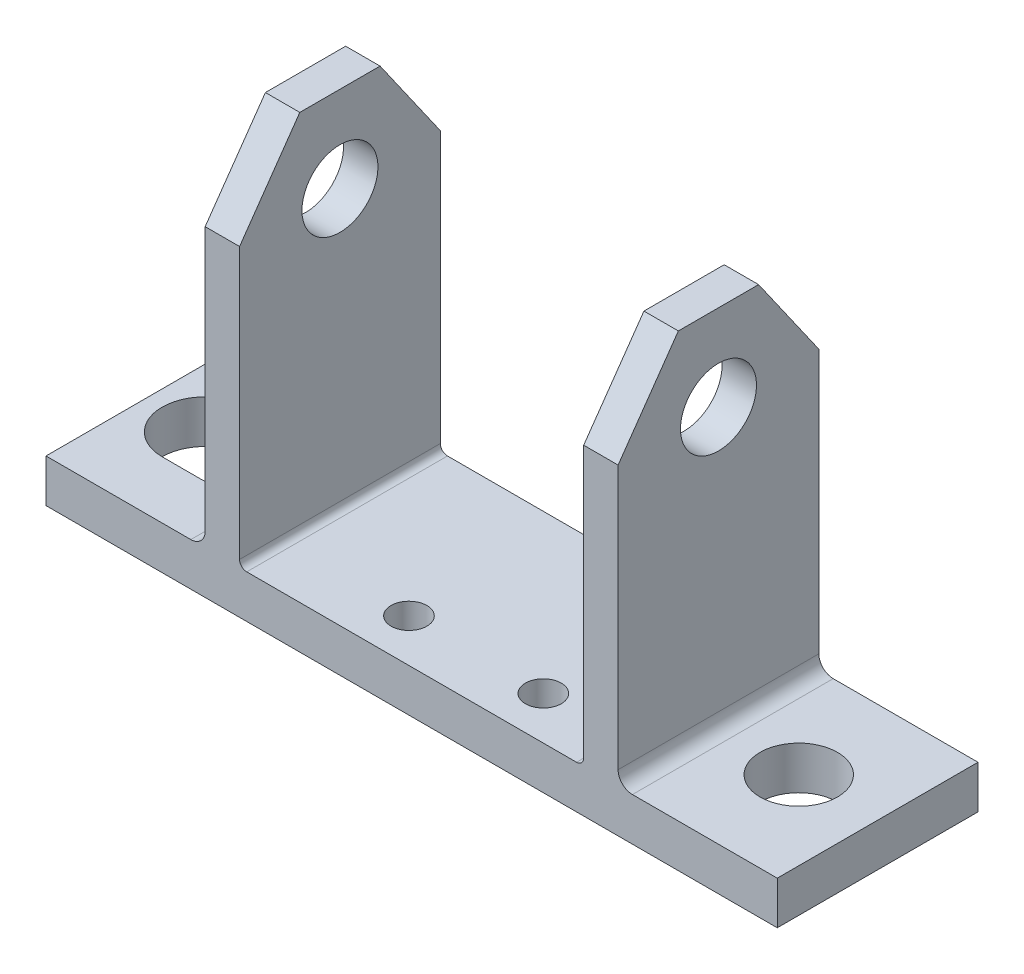
SolidWorks part; units mm, degrees
ref_plane "Front Plane" through (0, 0, 0) normal (0, 0, 1) x (1, 0, 0)
ref_plane "Top Plane" through (0, 0, 0) normal (0, 1, 0) x (1, 0, 0)
ref_plane "Right Plane" through (0, 0, 0) normal (1, 0, 0) x (0, 0, -1)
sketch "Sketch1" plane through (0, 0, 0) normal (0, 1, 0) x (1, 0, 0)
  line L0 (4.1, 7) -> (6.9, 7) construction
  line L1 (0, 0) -> (51, 0)
  line L2 (0, 0) -> (0, 14)
  line L3 (0, 14) -> (51, 14)
  line L4 (51, 0) -> (51, 14)
  line L5 (0, 0) -> (51, 14) construction
  line L6 (0, 14) -> (51, 0) construction
  line L7 (4.1, 10) -> (6.9, 10)
  line L8 (4.1, 4) -> (6.9, 4)
  line L12 (25.5, 14) -> (25.5, 0) construction
  arc A0 (4.1, 10) -> (4.1, 4) centre (4.1, 7) ccw
  arc A1 (6.9, 4) -> (6.9, 10) centre (6.9, 7) ccw
  circle A2 centre (45.5, 7) radius 2.7
  point P4 (25.5, 7)
  point P8 (5.5, 7)
  dimension "D3" = 3
  dimension "D4" = 2.8
  dimension "D5" = 5.4
  dimension "D1" = 51
  dimension "D2" = 14
  dimension "D6" = 40
  dimension "D7" = 20
  dimension "D8" = 7
extrude "Boss-Extrude1" add sketch "Sketch1" along normal blind 3
sketch "Sketch2" plane through (0, 3, 0) normal (0, 1, 0) x (1, 0, 0)
  line L0 (51, 14) -> (0, 14) construction
  line L1 (13.5, 14) -> (11.1, 14)
  line L2 (13.5, 14) -> (13.5, 0)
  line L3 (13.5, 0) -> (11.1, 0)
  line L4 (11.1, 14) -> (11.1, 0)
  line L5 (13.5, 14) -> (11.1, 0) construction
  line L6 (13.5, 0) -> (11.1, 14) construction
  line L7 (0, 0) -> (51, 0) construction
  line L8 (25.5, 14) -> (25.5, 0) construction
  line L9 (37.5, 0) -> (39.9, 14) construction
  line L10 (37.5, 14) -> (39.9, 0) construction
  line L11 (39.9, 14) -> (39.9, 0)
  line L12 (37.5, 0) -> (39.9, 0)
  line L13 (37.5, 14) -> (37.5, 0)
  line L14 (37.5, 14) -> (39.9, 14)
  point P4 (12.3, 7)
  point P15 (38.7, 7)
  dimension "D1" = 2.4
  dimension "D2" = 12
extrude "Boss-Extrude2" add sketch "Sketch2" along normal blind 25.4
sketch "Sketch3" plane through (0, 3, 0) normal (0, 1, 0) x (1, 0, 0)
  line L0 (17, 3) -> (37, 3) construction
  line L1 (13.5, 0) -> (37.5, 0) construction
  line L2 (37.5, 14) -> (37.5, 0) construction
  circle A0 centre (22.314, 3) radius 1.25
  circle A1 centre (31.686, 3) radius 1.25
  dimension "D1" = 2.5
  dimension "D2" = 9.372
  dimension "D3" = 3
  dimension "D4" = 20
  dimension "D5" = 5.314
  dimension "D6" = 0.5
extrude "Cut-Extrude1" cut sketch "Sketch3" against normal up to next
sketch "Sketch4" plane through (11.1, 0, 0) normal (-1, 0, 0) x (0, 0, 1)
  line L0 (-14, 28.4) -> (0, 28.4) construction
  line L1 (-14, 28.4) -> (-14, 3) construction
  circle A0 centre (-7, 22.4) radius 2.65
  dimension "D1" = 5.3
  dimension "D2" = 6
  dimension "D3" = 7
extrude "Cut-Extrude2" cut sketch "Sketch4" against normal through all
sketch "Sketch5" plane through (11.1, 0, 0) normal (-1, 0, 0) x (0, 0, 1)
  line L0 (-14, 22.4) -> (-9.7988, 28.4)
  line L1 (-14, 28.4) -> (-14, 3) construction
  line L2 (-14, 28.4) -> (0, 28.4) construction
  line L3 (-9.7988, 28.4) -> (-14, 28.4)
  line L4 (-14, 28.4) -> (-14, 22.4)
  line L5 (-7, 28.4) -> (-7, 22.4) construction
  line L6 (0, 22.4) -> (-4.2012, 28.4)
  line L7 (0, 28.4) -> (0, 22.4)
  line L8 (-4.2012, 28.4) -> (0, 28.4)
  circle A0 centre (-7, 22.4) radius 2.65 construction
  circle A1 centre (-7, 22.4) radius 2.65 construction
  dimension "D1" = 35
extrude "Cut-Extrude3" cut sketch "Sketch5" against normal through all
fillet "Fillet1" radius 1 2 edges at (39.9, 3, -7)
fillet "Fillet2" radius 0.5 2 edges at (37.5, 3, -7)
